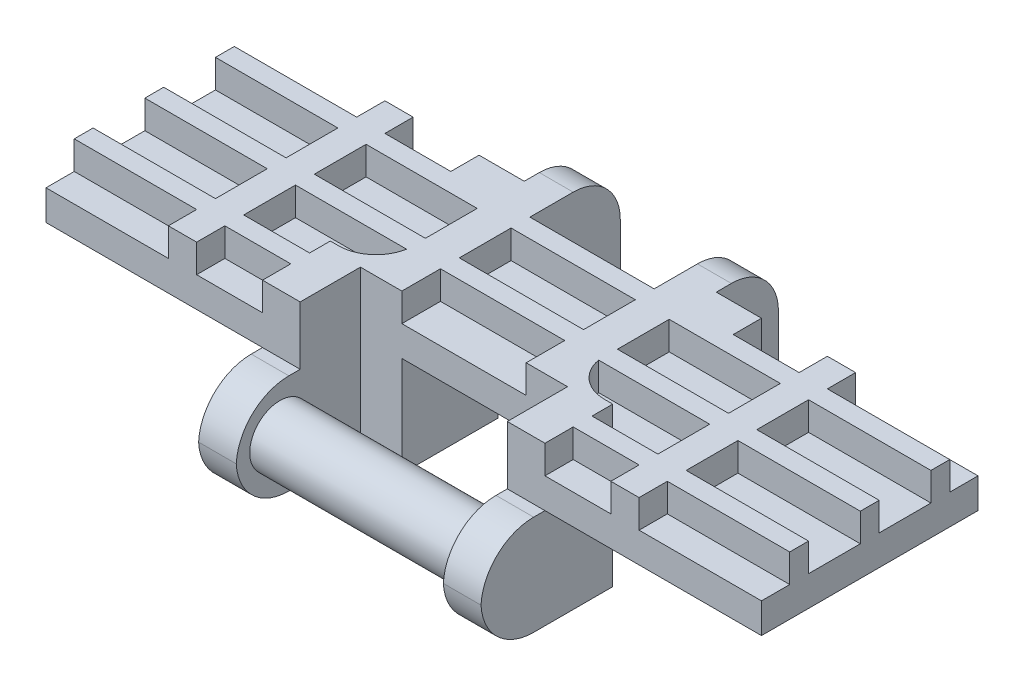
SolidWorks part; units mm, degrees
ref_plane "前视基准面" through (0, 0, 0) normal (0, 0, 1) x (1, 0, 0)
ref_plane "上视基准面" through (0, 0, 0) normal (0, 1, 0) x (1, 0, 0)
ref_plane "右视基准面" through (0, 0, 0) normal (1, 0, 0) x (0, 0, -1)
other "Configuration Table"
sketch "草图1" plane through (0, 0, 0) normal (0, 1, 0) x (1, 0, 0)
  line L1 (-19, -5.75) -> (19, -5.75)
  line L2 (-19, -5.75) -> (-19, 5.75)
  line L3 (-19, 5.75) -> (19, 5.75)
  line L4 (19, -5.75) -> (19, 5.75)
  line L5 (-19, -5.75) -> (19, 5.75) construction
  line L6 (-19, 5.75) -> (19, -5.75) construction
  line L13 (-19, 4.25) -> (19, 4.25)
  line L14 (-19, 4.25) -> (-19, 3.25)
  line L15 (-19, 3.25) -> (19, 3.25)
  line L16 (19, 4.25) -> (19, 3.25)
  line L17 (-19, 0.5) -> (19, 0.5)
  line L18 (-19, 0.5) -> (-19, -0.5)
  line L19 (-19, -0.5) -> (19, -0.5)
  line L20 (19, 0.5) -> (19, -0.5)
  line L21 (-19, -3.25) -> (19, -3.25)
  line L22 (-19, -3.25) -> (-19, -4.25)
  line L23 (-19, -4.25) -> (19, -4.25)
  line L24 (19, -3.25) -> (19, -4.25)
  line L25 (-12.5, 5.75) -> (-11, 5.75)
  line L26 (-12.5, 5.75) -> (-12.5, -5.75)
  line L27 (-12.5, -5.75) -> (-11, -5.75)
  line L28 (-11, 5.75) -> (-11, -5.75)
  line L29 (12.5, 5.75) -> (11, 5.75)
  line L30 (12.5, 5.75) -> (12.5, -5.75)
  line L31 (12.5, -5.75) -> (11, -5.75)
  line L32 (11, 5.75) -> (11, -5.75)
  point P0 (0, 0)
  point P6 (0, 0)
  dimension "D1" = 38
  dimension "D2" = 11.5
  dimension "D3" = 11
  dimension "D4" = 11
  dimension "D5" = 1
  dimension "D6" = 1.5
  dimension "D7" = 1.5
  dimension "D8" = 5.25
  dimension "D9" = 1.5
extrude "凸台-拉伸1" add sketch "草图1" along normal blind 1.6 contours L2 L3 L4 L1
extrude "凸台-拉伸2" add sketch "草图1<3>" along normal blind 1.5 from surface contours L13 L16 L15 L14 | L17 L20 L19 L18 | L21 L24 L23 L22 | L26 L27 L28 L25 | L30 L31 L32 L29 starting at face at (0, 1.6, 0)
sketch "草图1<3>" plane through (0, 0, 0) normal (0, 1, 0) x (1, 0, 0) same geometry as "草图1"
sketch "草图2" plane through (0, 0, 0) normal (0, 1, 0) x (1, 0, 0)
  line L0 (0, 0) -> (0, -13.8005) construction
  line L1 (-5.1, 9.05) -> (5.1, 9.05)
  line L2 (-5.1, 9.05) -> (-5.1, -2.55)
  line L3 (-5.1, -2.55) -> (5.1, -2.55)
  line L4 (5.1, 9.05) -> (5.1, -2.55)
  line L5 (-7.5, -2.55) -> (7.5, -2.55)
  line L6 (11, 4.25) -> (-11, 4.25) construction
  line L7 (-7.5, 5.75) -> (-5.1, 5.75)
  line L8 (-3.3, 9.05) -> (3.3, 9.05)
  line L9 (-3.3, 9.05) -> (-3.3, -2.55)
  line L10 (-3.3, -2.55) -> (3.3, -2.55)
  line L11 (3.3, 9.05) -> (3.3, -2.55)
  line L16 (-11, -5.75) -> (11, -5.75) construction
  line L17 (-11, 5.75) -> (11, 5.75) construction
  line L18 (-5.5, -2.15) -> (-5.5, -9.15)
  line L19 (-7.5, -2.15) -> (7.5, -2.15)
  line L20 (-7.5, -2.15) -> (-7.5, -9.15)
  line L21 (-7.5, -9.15) -> (7.5, -9.15)
  line L22 (7.5, -2.15) -> (7.5, -9.15)
  line L23 (5.5, -2.15) -> (5.5, -9.15)
  line L24 (-7.5, 5.75) -> (-7.5, 4.25)
  line L25 (-7.5, 4.25) -> (-5.1, 4.25)
  line L26 (-5.1, 5.75) -> (-5.1, 4.25)
  line L27 (7.5, 5.75) -> (5.1, 5.75)
  line L28 (7.5, 5.75) -> (7.5, 4.25)
  line L29 (7.5, 4.25) -> (5.1, 4.25)
  line L30 (5.1, 5.75) -> (5.1, 4.25)
  point P5 (0, -2.55)
  point P15 (0, 9.05)
  point P20 (0, -9.15)
  point P38 (0, 0)
  dimension "D1" = 10.2
  dimension "D2" = 3.2
  dimension "D3" = 6.6
  dimension "D4" = 3.3
  dimension "D5" = 15
  dimension "D6" = 2
  dimension "D7" = 2
  dimension "D8" = 3.4
  dimension "D9" = 7
extrude "凸台-拉伸3" add sketch "草图2" against normal blind 8.4 from surface contours L1 L11 L3 L4 | L9 L1 L2 L3 | L20 L21 L18 L19 | L19 L23 L21 L22 | L19 L18 L5 L2 | L19 L20 L5 L18 | L19 L2 L3 L9 | L19 L11 L3 L4 | L23 L19 L4 L5 | L19 L23 L5 L22 region at (-4.2, 0, -3.45) region at (4.2, 0, -3.45) region at (-4.2, 0, 2.35) region at (4.2, 0, 2.35) region at (-5.3, 0, 2.35) region at (5.3, 0, 2.35) region at (-6.5, 0, 2.35) region at (6.5, 0, 2.35) region at (-6.5, 0, 5.85) region at (6.5, 0, 5.85) starting at face at (0, 3.1, 0)
extrude "凸台-拉伸5" add sketch "草图2<4>" along normal up to surface (3.1 mm away) contours L27 L30 L29 L28 | L7 L26 L25 L24 up to face at (0, 3.1, -1.875)
sketch "草图2<4>" plane through (0, 0, 0) normal (0, 1, 0) x (1, 0, 0) same geometry as "草图2"
extrude "切除-拉伸1" cut sketch "草图2<3>" along normal through all contours L0 L5 L3 L18 L21 | L10 L0 L21 L23 L5 L3 region at (2.75, 0, 5.85) region at (-2.75, 0, 5.85)
sketch "草图2<3>" plane through (0, 0, 0) normal (0, 1, 0) x (1, 0, 0) same geometry as "草图2"
fillet "圆角1" radius 3 2 edges at (5.1, -2.65, 2.15) (-5.1, -2.65, 2.15)
sketch "草图3" plane through (-5.5, 0, 0) normal (1, 0, 0) x (0, 0, -1)
  line L1 (5.75, 3.1) -> (5.75, 0) construction
  line L2 (-6.83, -2.5) -> (5.75, -2.5)
  line L3 (2.55, -3.6) -> (9.05, -3.6)
  line L4 (2.55, -3.6) -> (2.55, -5.3)
  line L5 (2.55, -5.3) -> (9.05, -5.3)
  line L6 (9.05, -3.6) -> (9.05, -5.3)
  line L7 (-9.15, -5.3) -> (-9.15, 3.1) construction
  line L8 (-5.75, 3.1) -> (-9.15, 3.1)
  line L9 (-5.75, 3.1) -> (-5.75, 0)
  line L10 (-5.75, 0) -> (-9.15, 0)
  line L11 (-9.15, 3.1) -> (-9.15, 0)
  circle A0 centre (-6.83, -2.5) radius 1.6
  circle A1 centre (5.75, -2.5) radius 1.7
  dimension "D1" = 3.2
  dimension "D3" = 3.4
  dimension "D2" = 2.5
  dimension "D4" = 1.7
  dimension "D5" = 6.5
  dimension "D6" = 12.58
extrude "凸台-拉伸4" add sketch "草图3" along normal up to next contours A0
extrude "切除-拉伸2" cut sketch "草图3<3>" along normal through all both and the other way through all contours L3 L6 L5 L4 | A1 | L11 L10 L9 L8
sketch "草图3<3>" plane through (-5.5, 0, 0) normal (1, 0, 0) x (0, 0, -1) same geometry as "草图3"
fillet "圆角2" radius 2.8 4 edges at (6.5, -5.3, 9.15) (-6.5, -5.3, 9.15) (-6.5, 0, 9.15) (6.5, 0, 9.15)
fillet "圆角3" radius 2.5 2 edges at (-4.2, 3.1, -9.05) (4.2, 3.1, -9.05)
fillet "圆角4" radius 1 2 edges at (-4.2, -3.6, -9.05) (4.2, -3.6, -9.05)
fillet "圆角5" radius 0.5 4 edges at (-4.2, -3.6, -7.0461) (4.2, -3.6, -7.0461) (4.2, -3.6, -4.4539) (-4.2, -3.6, -4.4539)
fillet "圆角6" radius 2 2 edges at (5.1, 2.35, 2.15) (-5.1, 2.35, 2.15)
